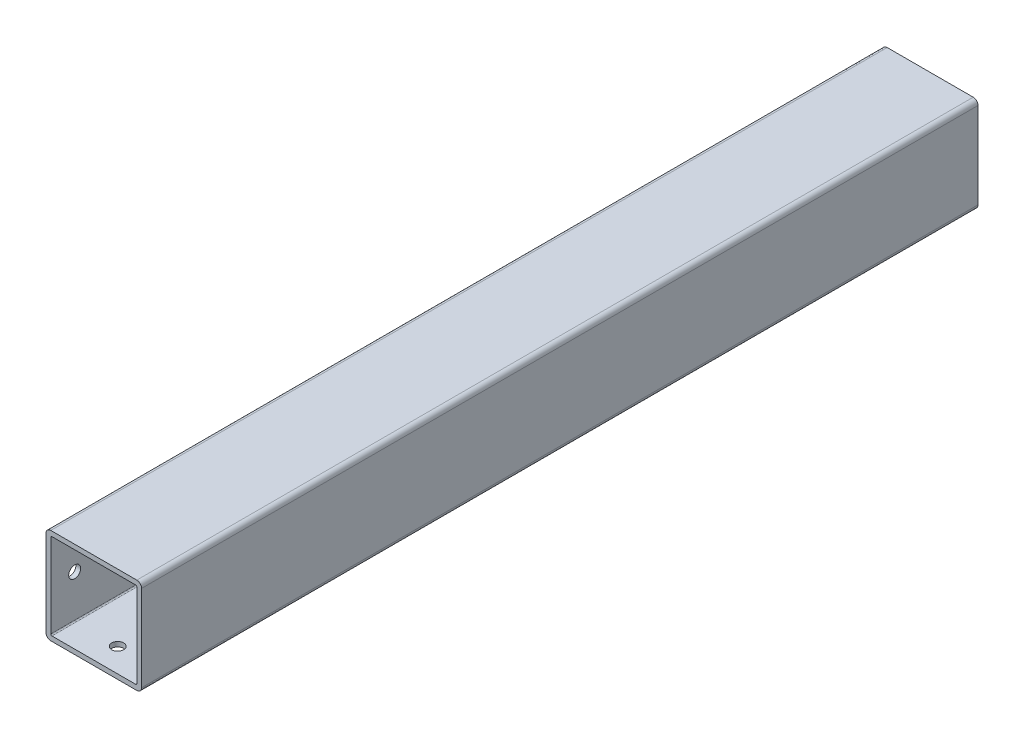
SolidWorks part; units mm, degrees
note: '?' marks a value the reader was unsure of.
ref_plane "Front Plane" through (0, 0, 0) normal (0, 0, 1) x (1, 0, 0)
ref_plane "Top Plane" through (0, 0, 0) normal (0, 1, 0) x (1, 0, 0)
ref_plane "Right Plane" through (0, 0, 0) normal (1, 0, 0) x (0, 0, -1)
sketch "Sketch1" plane through (0, 0, 0) normal (0, 0, 1) x (1, 0, 0)
  line L1 (-20, 20) -> (20, 20)
  line L2 (-20, 20) -> (-20, -20)
  line L3 (-20, -20) -> (20, -20)
  line L4 (20, 20) -> (20, -20)
  line L5 (-20, 20) -> (20, -20) construction
  line L6 (-20, -20) -> (20, 20) construction
  point P0 (0, 0)
  dimension "D1" = 40
  dimension "D2" = 40
extrude "Extrude-Thin1" add sketch "Sketch1" along normal blind 350 thin
fillet "Fillet1" radius 0.5 4 edges at (-18, -18, 175) (-18, 18, 175) (18, 18, 175) (18, -18, 175)
fillet "Fillet2" radius 2 4 edges at (20, -20, 175) (-20, -20, 175) (20, 20, 175) (-20, 20, 175)
sketch "Sketch2" plane through (0, 0, 0) normal (1, 0, 0) x (0, 0, -1)
  line L0 (-340, 0) -> (-350, 0) construction
  line L1 (-350, -18) -> (-350, 18) construction
  line L2 (-340, 0) -> (-315, 0) construction
  circle A0 centre (-340, 0) radius 2.5
  circle A1 centre (-315, 0) radius 2.5
  dimension "D1" = 5
  dimension "D2" = 25
  dimension "D3" = 10
extrude "Cut-Extrude1" cut sketch "Sketch2" against normal through all
ref_axis "Axis1" through (0, 0, 367.5) along (0, 0, -1)?
pattern_circular "CirPattern1" count 2 every 90 about axis through (0, 0, 367.5) along (0, 0, -1) of "Cut-Extrude1"
equation "\"a\"= \"Beam Profile@Plasma Beta.SLDASM\""
equation "\"b\"= 2"
equation "\"L\"= 350"
equation "\"D5@Extrude-Thin1\"=\"b\""
equation "\"D1@Fillet2\"=\"b\""
equation "\"D1@Sketch1\"=\"a\""
equation "\"D2@Sketch1\"=\"a\""
equation "\"D1@Extrude-Thin1\"=\"L\""
